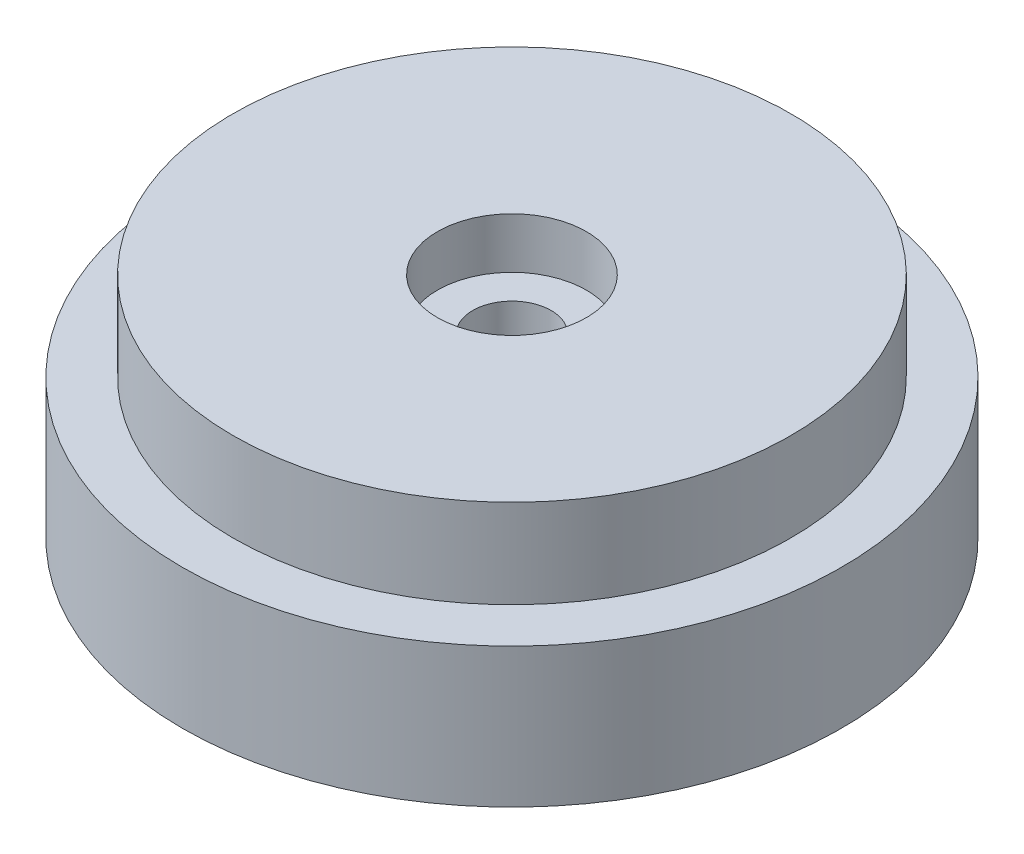
SolidWorks part; units mm, degrees
material "eSUN Tough Resin"
ref_plane "Front Plane" through (0, 0, 0) normal (0, 0, 1) x (1, 0, 0)
ref_plane "Top Plane" through (0, 0, 0) normal (0, 1, 0) x (1, 0, 0)
ref_plane "Right Plane" through (0, 0, 0) normal (1, 0, 0) x (0, 0, -1)
sketch "Sketch2" plane through (0, 0, 0) normal (0, 1, 0) x (1, 0, 0)
  line L0 (5, 5) -> (-5, -5) construction
  line L1 (-5, 5) -> (5, -5) construction
  circle A0 centre (0, 0) radius 11
  circle A10 centre (-5, 5) radius 3.05
  circle A11 centre (5, 5) radius 3.05
  circle A12 centre (5, -5) radius 3.05
  circle A13 centre (-5, -5) radius 3.05
  circle A14 centre (0, 0) radius 2.94
  circle A15 centre (0, 0) radius 1.55
  circle A16 centre (0, 0) radius 13
  dimension "D1" = 22
  dimension "D2" = 6.1
  dimension "D3" = 26
  dimension "D7" = 3.1
  dimension "D8" = 5.88
  dimension "D4" = 10
extrude "Boss-Extrude1" add sketch "Sketch2" along normal blind 9 contours A0 A14 A13 A12 A11 A10 | A12 | A11 | A10 | A13 region at (-10.6889, 0, 0) region at (-5, 0, -5) region at (5, 0, -5) region at (5, 0, 5) region at (-5, 0, 5)
extrude "Boss-Extrude2" add sketch "Sketch2<3>" along normal blind 7 contours A14 A15 region at (-2.8568, 0, 0)
sketch "Sketch2<3>" plane through (0, 0, 0) normal (0, 1, 0) x (1, 0, 0) same geometry as "Sketch2"
extrude "Cut-Extrude1" cut sketch "Sketch2<4>" along normal blind 3 contours A14 A15 region at (-2.8568, 0, 0)
sketch "Sketch2<4>" plane through (0, 0, 0) normal (0, 1, 0) x (1, 0, 0) same geometry as "Sketch2"
extrude "Cut-Extrude2" cut sketch "Sketch2<6>" along normal blind 8.6 contours A11 | A12 | A13 | A10 region at (-5, 0, -5) region at (5, 0, -5) region at (5, 0, 5) region at (-5, 0, 5)
sketch "Sketch2<6>" plane through (0, 0, 0) normal (0, 1, 0) x (1, 0, 0) same geometry as "Sketch2"
extrude "Boss-Extrude3" add sketch "Sketch2<7>" along normal blind 5.5 contours A16 A0 region at (-12.6323, 0, 0)
sketch "Sketch2<7>" plane through (0, 0, 0) normal (0, 1, 0) x (1, 0, 0) same geometry as "Sketch2"
